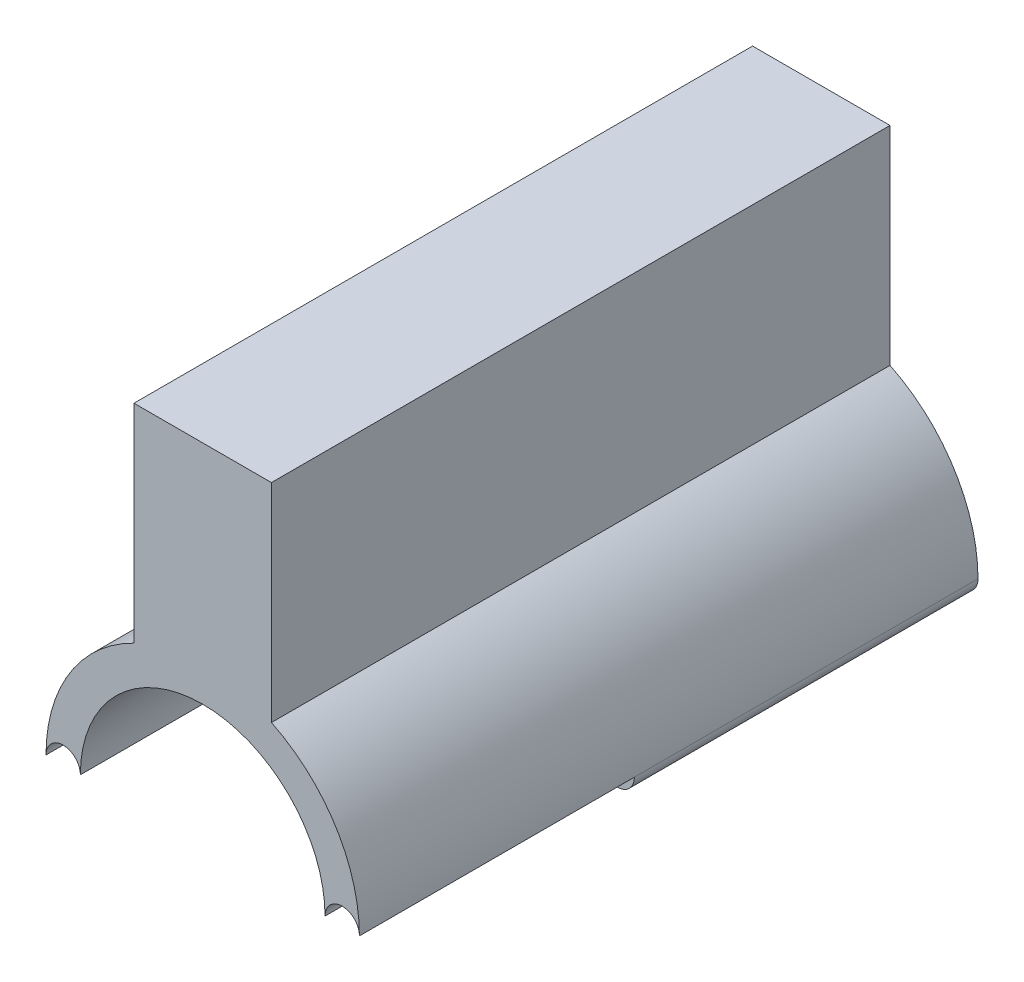
SolidWorks part; units mm, degrees
material "Commercialement pur CP-Ti UNS R50400 (SS)"
ref_plane "Plan de face" through (0, 0, 0) normal (0, 0, 1) x (1, 0, 0)
ref_plane "Plan de dessus" through (0, 0, 0) normal (0, 1, 0) x (1, 0, 0)
ref_plane "Plan de droite" through (0, 0, 0) normal (1, 0, 0) x (0, 0, -1)
sketch "Esquisse1" plane through (0, 0, 0) normal (0, 0, 1) x (1, 0, 0)
  line L1 (-50, 73.6274) -> (-50, 253.6274)
  line L2 (-50, 253.6274) -> (50, 253.6274)
  line L3 (50, 253.6274) -> (50, 73.6274)
  arc A0 (89, 0) -> (-89, 0) centre (0, 0) ccw
  arc A1 (114, 0) -> (-114, 0) centre (0, 0) ccw
  arc A2 (-114, 0) -> (-89, 0) centre (-101.5, 0) ccw
  arc A3 (89, 0) -> (114, 0) centre (101.5, 0) ccw
  dimension "D1" = 178
  dimension "D2" = 228
  dimension "D3" = 50
  dimension "D4" = 50
  dimension "D5" = 180
extrude "Boss.-Extru.1" add sketch "Esquisse1" along normal blind 450 contours A1 L3 L2 L1 | L1 A1 A2 A0 | L3 A1 L1 A0 | A3 A1 L3 A0 region at (-85.63, 44.7063, 0) region at (0, 96.9824, 0) region at (0, 181.8888, 0) region at (85.63, 44.7063, 0)
sketch "Esquisse2" plane through (0, 0, 450) normal (0, 0, 1) x (1, 0, 0)
  circle A1 centre (101.5, 0) radius 7.5
  circle A2 centre (-101.5, 0) radius 7.5
  circle A3 centre (-101.5, 0) radius 12.5
  circle A4 centre (101.5, 0) radius 12.5
  dimension "D1" = 15
  dimension "D2" = 15
extrude "Enlèv. mat.-Extru.1" cut sketch "Esquisse2" against normal blind 350 contours A2 | A1
extrude "Enlèv. mat.-Extru.2" cut sketch "Esquisse2<3>" against normal blind 200
sketch "Esquisse2<3>" plane through (0, 0, 450) normal (0, 0, 1) x (1, 0, 0) same geometry as "Esquisse2"
